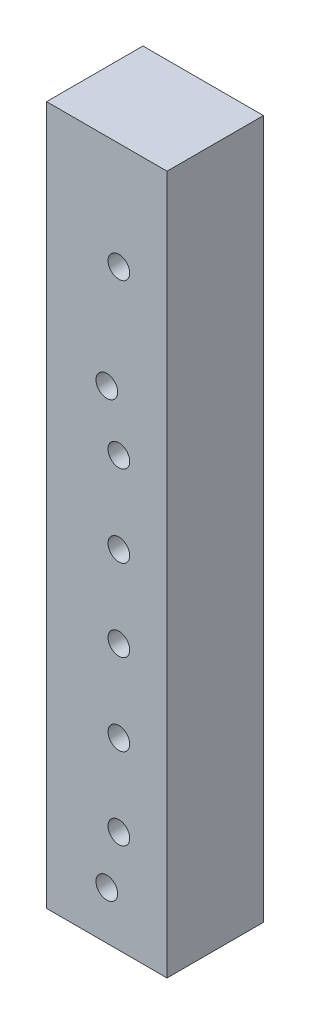
SolidWorks part; units mm, degrees
ref_plane "前基準面" through (0, 0, 0) normal (0, 0, 1) x (1, 0, 0)
ref_plane "上基準面" through (0, 0, 0) normal (0, 1, 0) x (1, 0, 0)
ref_plane "右基準面" through (0, 0, 0) normal (1, 0, 0) x (0, 0, -1)
sketch "草圖1" plane through (0, 0, 0) normal (0, 1, 0) x (1, 0, 0)
  line L1 (-7.5, 6) -> (7.5, 6)
  line L2 (-7.5, 6) -> (-7.5, -6)
  line L3 (-7.5, -6) -> (7.5, -6)
  line L4 (7.5, 6) -> (7.5, -6)
  line L5 (-7.5, 6) -> (7.5, -6) construction
  line L6 (-7.5, -6) -> (7.5, 6) construction
  point P0 (0, 0)
  dimension "D1" = 12
  dimension "D2" = 15
extrude "填料-伸長1" add sketch "草圖1" along normal blind 87
sketch "草圖2" plane through (0, 87, 0) normal (0, 1, 0) x (1, 0, 0)
  point P0 (0, 0)
sketch "草圖4" plane through (0, 0, -6) normal (0, 0, -1) x (-1, 0, 0)
  line L0 (7.5, 87) -> (7.5, 0) construction
  line L1 (55, 0) -> (-55, 0) construction
  line L2 (-1.5, 12.73) -> (-1.5, 33.05) construction
  point P0 (-1.5, 12.73)
  point P5 (-1.5, 33.05)
  point P6 (-1.5, 53.37)
  point P7 (-1.5, 73.69)
  dimension "D1" = 9
  dimension "D2" = 12.73
  dimension "D4" = 20.32
  dimension "D3" = 4
hole_wizard "Ø2.7 (2.7) 直徑孔2" positions "3D草圖2" profile "草圖5" hole size "Ø2.7" standard "GB" end condition through all
sketch3d "3D草圖2"
  point P0 (1.5, 12.73, -6)
  point P3 (1.5, 33.05, -6)
  point P6 (1.5, 53.37, -6)
  point P9 (1.5, 73.69, -6)
sketch "草圖5" plane through (1.5, 12.73, -6) normal (1, 0, 0) x (0, 1, 0)
  line L0 (0, 0) -> (0, 12)
  line L1 (0, 12) -> (1.35, 12)
  line L2 (1.35, 12) -> (1.35, 0)
  line L5 (1.35, 0) -> (0, 0)
  line L11 (0, -6.35) -> (0, 107.95) construction
  dimension "貫穿孔直徑" = 2.7
  dimension "貫穿孔深度" = 12
sketch "草圖6" plane through (0, 0, -6) normal (0, 0, -1) x (-1, 0, 0)
  line L2 (55, 0) -> (-55, 0) construction
  line L3 (7.5, 87) -> (7.5, 0) construction
  point P0 (0, 60.1)
  point P1 (0, 6)
  dimension "D1" = 54.1
  dimension "D2" = 7.5
  dimension "D3" = 6
  dimension "D4" = 7.5
hole_wizard "Ø2.7 (2.7) 直徑孔1" positions "3D草圖3" profile "草圖7" hole size "Ø2.7" standard "GB" end condition through all
sketch3d "3D草圖3"
  point P0 (0, 60.1, -6)
  point P3 (0, 6, -6)
sketch "草圖7" plane through (0, 60.1, -6) normal (1, 0, 0) x (0, 1, 0)
  line L0 (0, 0) -> (0, 12)
  line L1 (0, 12) -> (1.35, 12)
  line L2 (1.35, 12) -> (1.35, 0)
  line L5 (1.35, 0) -> (0, 0)
  line L11 (0, -6.35) -> (0, 107.95) construction
  dimension "貫穿孔直徑" = 2.7
  dimension "貫穿孔深度" = 12
sketch "草圖8" plane through (0, 0, -6) normal (0, 0, -1) x (-1, 0, 0)
  line L0 (-1.5, 12.73) -> (-1.5, 33.05) construction
  line L1 (-1.5, 22.89) -> (-1.5, 43.21) construction
  point P0 (-1.5, 22.89)
  point P5 (-1.5, 43.21)
  point P6 (-1.5, 63.53)
  dimension "D2" = 20.32
  dimension "D1" = 3
hole_wizard "Ø2.7 (2.7) 直徑孔3" positions "3D草圖4" profile "草圖9" hole size "Ø2.7" standard "GB" end condition through all
sketch3d "3D草圖4"
  point P0 (1.5, 22.89, -6)
  point P3 (1.5, 43.21, -6)
sketch "草圖9" plane through (1.5, 22.89, -6) normal (1, 0, 0) x (0, 1, 0)
  line L0 (0, 0) -> (0, 12)
  line L1 (0, 12) -> (1.35, 12)
  line L2 (1.35, 12) -> (1.35, 0)
  line L5 (1.35, 0) -> (0, 0)
  line L11 (0, -6.35) -> (0, 107.95) construction
  dimension "貫穿孔直徑" = 2.7
  dimension "貫穿孔深度" = 12
